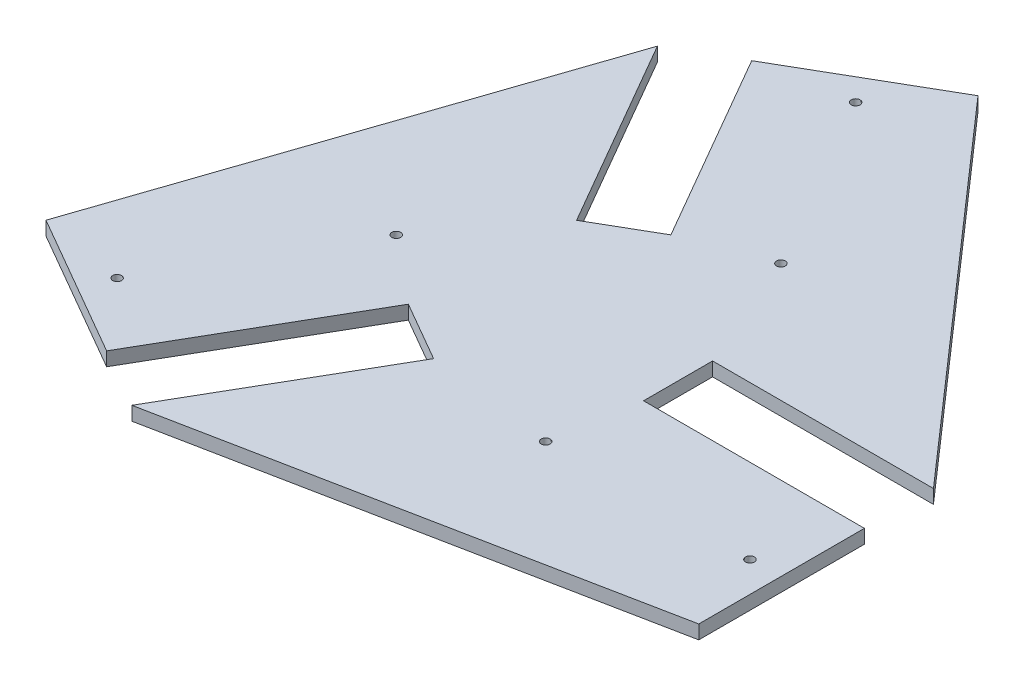
SolidWorks part; units mm, degrees
ref_plane "Front Plane" through (0, 0, 0) normal (0, 0, 1) x (1, 0, 0)
ref_plane "Top Plane" through (0, 0, 0) normal (0, 1, 0) x (1, 0, 0)
ref_plane "Right Plane" through (0, 0, 0) normal (1, 0, 0) x (0, 0, -1)
sketch "Sketch1" plane through (0, 0, 0) normal (0, 1, 0) x (1, 0, 0)
  line L0 (76.2, -47.5615) -> (76.2, 6.4135) construction
  line L1 (76.2, -47.5615) -> (-32.5457, -69.1979)
  line L2 (-43.6543, 62.7844) -> (-79.2895, -42.2104)
  line L5 (-79.2895, -42.2104) -> (-32.5457, -69.1979) construction
  line L6 (76.2, 6.4135) -> (25.4, 6.4135)
  line L7 (25.4, 6.4135) -> (25.4, -9.4615)
  line L8 (25.4, -9.4615) -> (76.2, -9.4615)
  line L9 (76.2, -9.4615) -> (76.2, -47.5615)
  line L10 (3.0895, 89.7719) -> (76.2, 6.4135)
  line L11 (-46.2939, -61.2604) -> (-79.2895, -42.2104)
  line L12 (-20.8939, -17.2663) -> (-46.2939, -61.2604)
  line L13 (-32.5457, -69.1979) -> (-7.1457, -25.2038)
  line L14 (-7.1457, -25.2038) -> (-20.8939, -17.2663)
  line L16 (3.0895, 89.7719) -> (-43.6543, 62.7844) construction
  line L17 (-29.9061, 70.7219) -> (3.0895, 89.7719)
  line L18 (-4.5061, 26.7278) -> (-29.9061, 70.7219)
  line L19 (-43.6543, 62.7844) -> (-18.2543, 18.7903)
  line L20 (-18.2543, 18.7903) -> (-4.5061, 26.7278)
  line L21 (0, 0) -> (-49999.9986, 0) construction
  line L22 (0, 0) -> (-25000, 43301.2702) construction
  line L23 (0, 0) -> (-25000, -43301.2702) construction
  line L24 (25.4, 0) -> (76.2, 0) construction
  line L25 (-12.7, -21.997) -> (-38.1, -65.9911) construction
  line L26 (-12.7, 21.997) -> (-38.1, 65.9911) construction
  line L27 (76.2, 8.001) -> (76.2, 45.974) [skipped]
  line L28 (-31.1709, -69.9916) -> (1.7147, -88.9781) [skipped]
  line L29 (-45.0291, 61.9906) -> (-77.9147, 43.0041) [skipped]
  circle A0 centre (69.2404, -28.829) radius 1.016
  circle A1 centre (0, 0) radius 76.2 construction
  circle A2 centre (-59.5868, -45.5494) radius 1.016
  circle A3 centre (-9.6536, 74.3784) radius 1.016
  circle A4 centre (22.2504, -28.829) radius 1.016
  circle A5 centre (-36.0918, -4.8549) radius 1.016
  circle A6 centre (13.8414, 33.6839) radius 1.016
  dimension "D2" = 15.875
  dimension "D6" = 152.4
  dimension "D13" = 2.032
  dimension "D17" = 2.032
  dimension "D1" = 120
  dimension "D3" = 50.8
  dimension "D4" = 38.1
  dimension "D5" = 3
  dimension "D7" = 9.4615
  dimension "D9" = 120
  dimension "D10" = 120
  dimension "D11" = 6.9596
  dimension "D12" = 19.3675
  dimension "D15" = 19.3675
  dimension "D16" = 53.9496
  dimension "D8" = 3
  dimension "D14" = 3
  dimension "D18" = 3
extrude "Boss-Extrude2" add sketch "Sketch1" along normal blind 3.175
